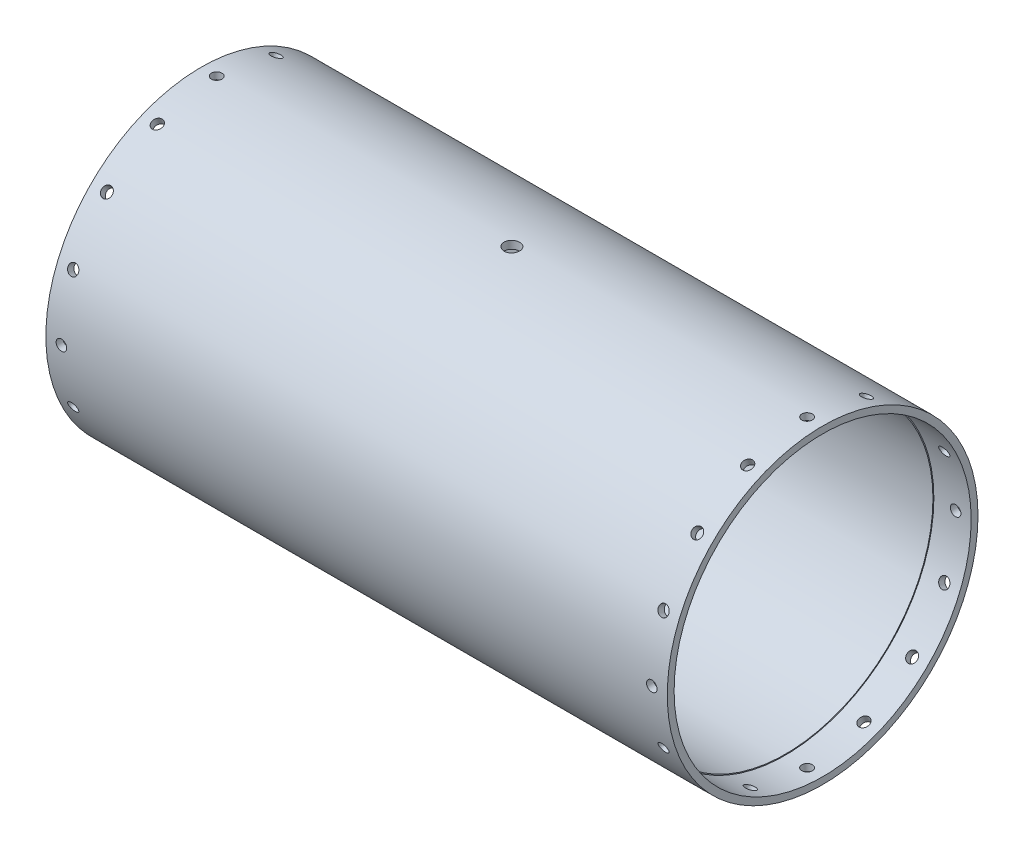
SolidWorks part; units mm, degrees
material "6061 Alloy"
ref_plane "Front Plane" through (0, 0, 0) normal (0, 0, 1) x (1, 0, 0)
ref_plane "Top Plane" through (0, 0, 0) normal (0, 1, 0) x (1, 0, 0)
ref_plane "Right Plane" through (0, 0, 0) normal (1, 0, 0) x (0, 0, -1)
sketch "Sketch1" plane through (0, 0, 0) normal (1, 0, 0) x (0, 0, -1)
  circle A0 centre (0, 0) radius 63.5
  circle A1 centre (0, 0) radius 60.325
  dimension "D1" = 127
  dimension "D2" = 3.175
extrude "Boss-Extrude1" add sketch "Sketch1" along normal blind 254
hole_wizard "#6 Clearance Hole1" positions "3DSketch1" profile "Sketch2" hole size "#6" standard "ANSI Inch" end condition up to next
sketch3d "3DSketch1"
  line L2 (0, 63.5, 0) -> (0, 0, 0) construction
  line L4 (0, 63.5, 0) -> (6.35, 63.5, 0) construction
  line L6 (6.35, 63.5, 0) -> (247.65, 63.5, 0) construction
  circle A1 centre (0, 0, 0) radius 63.5 construction
  point P0 (6.35, 63.5, 0)
  point P2 (247.65, 63.5, 0)
  point P16 (63.5, 0, 0)
  dimension "D2" = 6.35
  dimension "D1" = 6.35
sketch "Sketch2" plane through (6.35, 63.5, 0) normal (1, 0, 0) x (0, 0, 1)
  line L0 (0, 0) -> (0, 3.175)
  line L1 (0, 3.175) -> (2.1526, 3.175)
  line L2 (2.1526, 3.175) -> (2.1526, 0)
  line L5 (2.1526, 0) -> (0, 0)
  line L11 (0, -6.35) -> (0, 107.95) construction
  dimension "Thru Hole Dia." = 4.3053
  dimension "Thru Hole Depth" = 3.175
pattern_circular "CirPattern1" count 16 over 360 about axis through (254, 0, 0) along (-1, 0, 0) of "#6 Clearance Hole1" reverse direction yes
sketch "Sketch3" plane through (0, 0, 0) normal (0, 1, 0) x (1, 0, 0)
  line L0 (0, 0) -> (254, 0) construction
  line L1 (254, -63.5) -> (254, 63.5) construction
  circle A0 centre (127, 0) radius 3.175
  dimension "D1" = 6.35
extrude "Cut-Extrude1" cut sketch "Sketch3" against normal through all both and the other way through all
ref_axis "Axis1" through (6.35, 60.1651, 0) along (0, 1, 0)
ref_axis "Axis2" through (6.35, 54.1486, 22.4291) along (0, 0.9239, 0.3827)
ref_plane "Plane1" through (6.35, 0, 0) normal (1, 0, 0) x (0, 0, -1)
sketch "Sketch4" plane through (6.35, 0, 0) normal (1, 0, 0) x (0, 0, -1)
  line L0 (2.1526, 60.2866) -> (2.1526, 63.4635)
  line L1 (-2.1526, 63.4635) -> (-2.1526, 60.2866)
  line L2 (-2.1526, 63.4635) -> (-2.1526, 60.2866)
  line L3 (2.1526, 60.2866) -> (2.1526, 63.4635)
  line L4 (-21.0819, 56.5213) -> (-22.2976, 59.4564)
  line L5 (-26.2752, 57.8088) -> (-25.0595, 54.8738)
  line L6 (-26.2752, 57.8088) -> (-25.0595, 54.8738)
  line L7 (-21.0819, 56.5213) -> (-22.2976, 59.4564)
  line L8 (2.1526, 63.4635) -> (-2.1526, 63.4635) construction
  line L9 (-22.2976, 59.4564) -> (-26.2752, 57.8088) construction
  line L10 (0, 63.4635) -> (-9.4266, 75.7394)
  line L11 (-9.4266, 75.7394) -> (-27.0379, 62.2157)
  line L12 (-27.0379, 62.2157) -> (-24.2864, 58.6326)
  point P8 (0, 63.4635)
  point P9 (-24.2864, 58.6326)
  dimension "D1" = 22.2046
sketch "Sketch5" plane through (0, 0, 0) normal (-1, 0, 0) x (0, 0, 1)
  circle A0 centre (0, 0) radius 60.706
  circle A1 centre (0, 0) radius 63.5 construction
  dimension "D1" = 2.794
extrude "Cut-Extrude2" cut sketch "Sketch5" against normal blind 15.24
sketch "Sketch6" plane through (254, 0, 0) normal (1, 0, 0) x (0, 0, -1)
  circle A0 centre (0, 0) radius 60.706
  circle A1 centre (0, 0) radius 63.5 construction
  dimension "D1" = 2.794
extrude "Cut-Extrude3" cut sketch "Sketch6" against normal blind 15.24
equation "\"D2@3DSketch1\"=\"D1@3DSketch1\""
